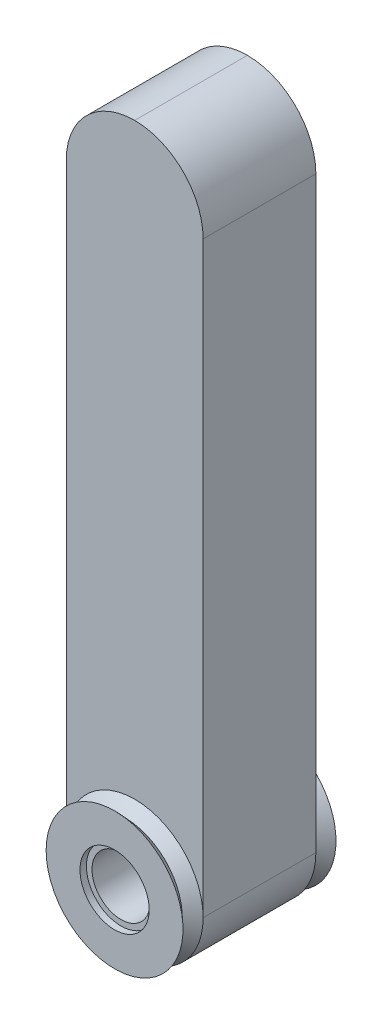
SolidWorks part; units mm, degrees
ref_plane "정면" through (0, 0, 0) normal (0, 0, 1) x (1, 0, 0)
ref_plane "윗면" through (0, 0, 0) normal (0, 1, 0) x (1, 0, 0)
ref_plane "우측면" through (0, 0, 0) normal (1, 0, 0) x (0, 0, -1)
sketch "스케치1" plane through (0, 0, 0) normal (0, 0, 1) x (1, 0, 0)
  line L1 (8.5, -45) -> (-8.5, -45)
  line L2 (8.5, -45) -> (8.5, 45)
  line L3 (8.5, 45) -> (-8.5, 45)
  line L4 (-8.5, -45) -> (-8.5, 45)
  line L5 (8.5, -45) -> (-8.5, 45) construction
  line L6 (8.5, 45) -> (-8.5, -45) construction
  circle A0 centre (0, -36.5) radius 3.6
  point P0 (0, 0)
  dimension "D3" = 7.2
  dimension "D1" = 90
  dimension "D2" = 17
  dimension "D4" = 36.5
extrude "보스-돌출1" add sketch "스케치1" along normal mid plane 14
fillet "필렛1" radius 8.5 4 edges at (8.5, -45, 0) (-8.5, -45, 0) (-8.5, 45, 0) (8.5, 45, 0)
sketch "스케치2" plane through (0, 0, 7) normal (0, 0, 1) x (1, 0, 0)
  circle A0 centre (0, -36.5) radius 8.5
  circle A1 centre (0, -36.5) radius 3.6
  dimension "D2" = 17
  dimension "D3" = 7.2
  dimension "D1" = 36.5
extrude "보스-돌출2" add sketch "스케치2" along normal blind 2.5
sketch "스케치3" plane through (0, 0, 0) normal (1, 0, 0) x (0, 0, -1)
  line L0 (-9.5, -28) -> (-8.25, -29.35)
  line L1 (-8.25, -29.35) -> (-7, -28)
  line L2 (-7, -36.5) -> (-7, 36.5) construction
  line L3 (-7, -28) -> (-7, -36.5) construction
  line L4 (-9.5, -28) -> (-7, -28)
  line L5 (0, -36.5) -> (-15.491, -36.5) construction
  line L6 (-7, -36.5) -> (7, -36.5) construction
  dimension "D1" = 1.35
  dimension "D2" = 1.25
revolve "컷-회전1" cut sketch "스케치3" angle 360 about L5
sketch "스케치4" plane through (0, 0, 9.5) normal (0, 0, 1) x (1, 0, 0)
  circle A0 centre (0, -36.5) radius 4.3
  dimension "D1" = 8.6
extrude "컷-돌출1" cut sketch "스케치4" against normal blind 0.8
mirror "대칭 복사1" about plane through (0, 0, 0) normal (0, 0, 1) of "컷-돌출1", "컷-회전1", "보스-돌출2"
